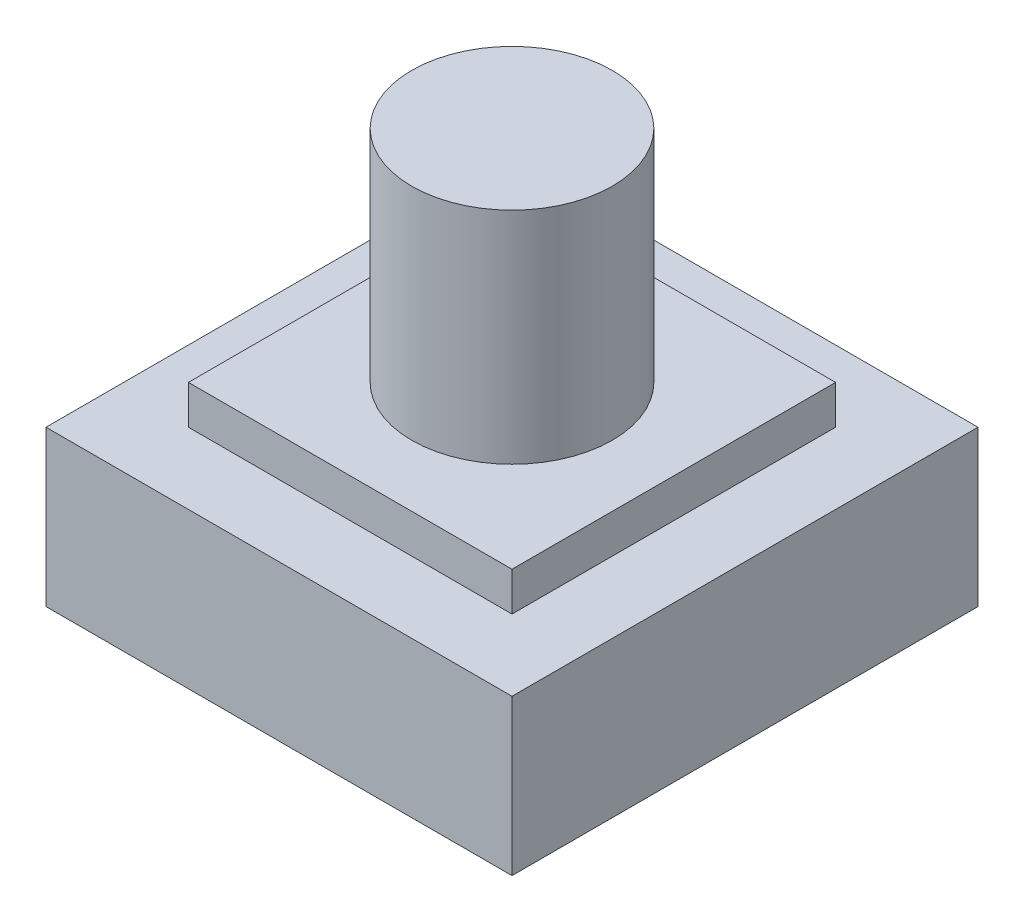
SolidWorks part; units mm, degrees
ref_plane "前视基准面" through (0, 0, 0) normal (0, 0, 1) x (1, 0, 0)
ref_plane "上视基准面" through (0, 0, 0) normal (0, 1, 0) x (1, 0, 0)
ref_plane "右视基准面" through (0, 0, 0) normal (1, 0, 0) x (0, 0, -1)
sketch "草图1" plane through (0, 0, 0) normal (0, 1, 0) x (1, 0, 0)
  line L1 (-18, -18) -> (18, -18)
  line L2 (-18, -18) -> (-18, 18)
  line L3 (-18, 18) -> (18, 18)
  line L4 (18, -18) -> (18, 18)
  line L5 (-18, -18) -> (18, 18) construction
  line L6 (-18, 18) -> (18, -18) construction
  line L7 (-12.5, 12.5) -> (12.5, 12.5)
  line L8 (-12.5, 12.5) -> (-12.5, -12.5)
  line L9 (-12.5, -12.5) -> (12.5, -12.5)
  line L10 (12.5, 12.5) -> (12.5, -12.5)
  line L11 (-12.5, 12.5) -> (12.5, -12.5) construction
  line L12 (-12.5, -12.5) -> (12.5, 12.5) construction
  circle A0 centre (0, 0) radius 7.75
  point P0 (0, 0)
  point P6 (0, 0)
  dimension "D4" = 15.5
  dimension "D1" = 36
  dimension "D2" = 36
  dimension "D3" = 25
extrude "凸台-拉伸2" add sketch "草图1" along normal blind 12 contours L1 L4 L3 L2 L7 L10 L9 L8 | A0 | L10 L7 L8 L9 A0 region at (-17.4909, 0, 0) region at (0, 0, -12.1464) region at (0, 0, 0)
extrude "凸台-拉伸3" add sketch "草图1<3>" along normal blind 3 from surface contours A0 | L10 L7 L8 L9 A0 region at (0, 0, -12.1464) region at (0, 0, 0) starting at face at (0, 12, 0)
sketch "草图1<3>" plane through (0, 0, 0) normal (0, 1, 0) x (1, 0, 0) same geometry as "草图1"
extrude "凸台-拉伸4" add sketch "草图1<5>" along normal blind 17 from surface separate body contours A0 region at (0, 0, 0) starting at face at (0, 15, 0)
sketch "草图1<5>" plane through (0, 0, 0) normal (0, 1, 0) x (1, 0, 0) same geometry as "草图1"
sketch "草图2" plane through (0, 0, 0) normal (0, -1, 0) x (1, 0, 0)
  line L0 (18, 18) -> (18, -18) construction
  line L1 (3, -11.8) -> (12, -11.8)
  line L2 (3, -11.8) -> (3, -16.5)
  line L3 (3, -16.5) -> (12, -16.5)
  line L4 (12, -11.8) -> (12, -16.5)
  line L5 (-18, -18) -> (18, -18) construction
  dimension "D1" = 6
  dimension "D2" = 15
  dimension "D3" = 1.5
  dimension "D4" = 6.2
extrude "凸台-拉伸5" add sketch "草图2" along normal blind 2
